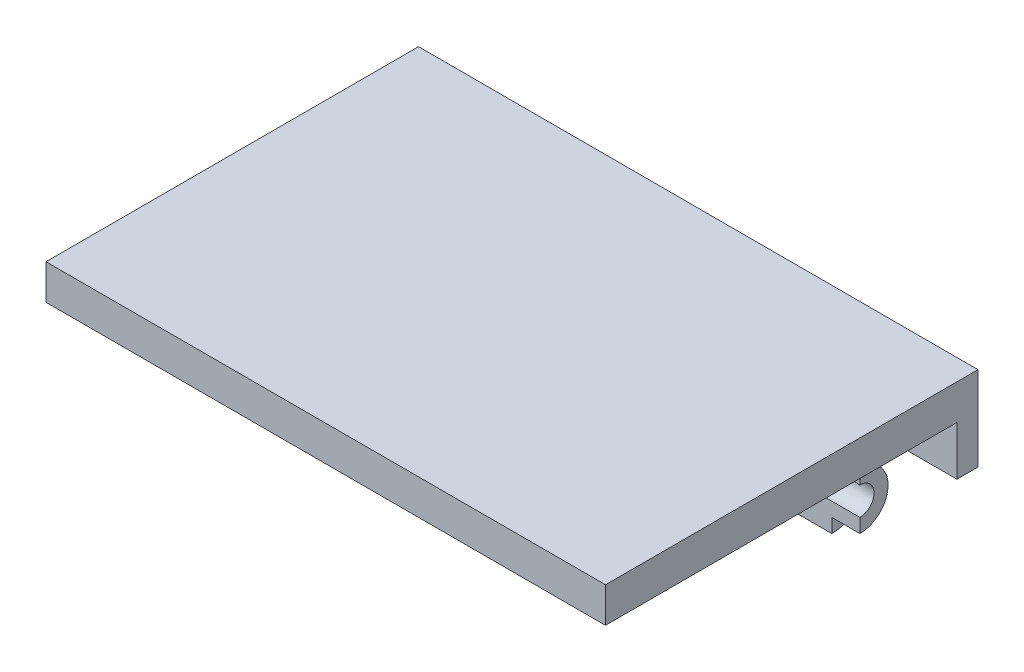
SolidWorks part; units mm, degrees
ref_plane "Ön Düzlem" through (0, 0, 0) normal (0, 0, 1) x (1, 0, 0)
ref_plane "Üst Düzlem" through (0, 0, 0) normal (0, 1, 0) x (1, 0, 0)
ref_plane "Sağ Düzlem" through (0, 0, 0) normal (1, 0, 0) x (0, 0, -1)
sketch "Çizim2" plane through (0, 0, 0) normal (0, 0, 1) x (1, 0, 0)
  line L1 (-47.2438, 23.3082) -> (-7.2438, 23.3082)
  line L2 (-47.2438, 23.3082) -> (-47.2438, 7.3082)
  line L3 (-47.2438, 7.3082) -> (-7.2438, 7.3082)
  line L4 (-7.2438, 23.3082) -> (-7.2438, 7.3082)
extrude "Yükseklik-Ekstrüzyon4" add sketch "Çizim2" along normal blind 9
sketch "Çizim3" plane through (-7.2438, 0, 0) normal (1, 0, 0) x (0, 0, -1)
  line L0 (-9, 7.3082) -> (-9, 23.3082) construction
  line L1 (-9, 21.3082) -> (-9, 9.3082)
  arc A0 (-9, 11.3082) -> (-9, 19.3082) centre (-9, 15.3082) ccw
  arc A1 (-9, 9.3082) -> (-9, 21.3082) centre (-9, 15.3082) ccw
  line M1 (0, 7.3082) -> (0, 23.3082)
  line M2 (0, 23.3082) -> (-9, 23.3082)
  line M3 (-9, 23.3082) -> (-9, 7.3082)
  line M4 (-9, 7.3082) -> (0, 7.3082)
extrude "Yükseklik-Ekstrüzyon5" add sketch "Çizim3" along normal blind 2 and the other way blind 42 contours A1 L1 A0 M3 region at (-7.2438, 15.3082, 3.1342)
extrude "Yükseklik-Ekstrüzyon6" add sketch "Çizim3<3>" along normal blind 6 and the other way blind 46 contours L1 A0 region at (-7.2438, 15.3082, 7.3023)
sketch "Çizim3<3>" plane through (-7.2438, 0, 0) normal (1, 0, 0) x (0, 0, -1) same geometry as "Çizim3"
sketch "Çizim4" plane through (-1.2438, 0, 0) normal (1, 0, 0) x (0, 0, -1)
  line L0 (-9, 17.3082) -> (-9, 13.3082)
  arc A3 (-9, 13.3082) -> (-9, 17.3082) centre (-9, 15.3082) ccw
extrude "Kes-Ekstrüzyon1" cut sketch "Çizim4" against normal blind 52
extrude "Kes-Ekstrüzyon2" cut sketch "Çizim3<4>" against normal blind 52 and the other way through all contours A1 L1 M4 M1 M2 M3 region at (-7.2438, 22.3082, 8.8164)
sketch "Çizim3<4>" plane through (-7.2438, 0, 0) normal (1, 0, 0) x (0, 0, -1) same geometry as "Çizim3"
sketch "Çizim7" plane through (-5.2438, 0, 0) normal (1, 0, 0) x (0, 0, -1)
  line L0 (-5, 19.7803) -> (-5, 24.3082)
  line L3 (-9, 21.3082) -> (-9, 24.3082)
  line L4 (-9, 24.3082) -> (-5, 24.3082)
  arc A1 (-9, 21.3082) -> (-5, 19.7803) centre (-9, 15.3082) cw
extrude "Yükseklik-Ekstrüzyon7" add sketch "Çizim7" against normal blind 44
sketch "Çizim8" plane through (0, 0, 9) normal (0, 0, 1) x (1, 0, 0)
  line L0 (-7.4438, 24.3082) -> (-7.4438, 21.3082)
  line L1 (-49.2438, 24.3082) -> (-47.0438, 24.3082)
  line L2 (-49.2438, 24.3082) -> (-49.2438, 22.3082)
  line L5 (-5.2438, 24.3082) -> (-7.4438, 24.3082)
  line L6 (-5.2438, 24.3082) -> (-5.2438, 22.3082)
  line L9 (-7.4438, 21.3082) -> (-5.2438, 21.3082)
  line L10 (-5.2438, 24.3082) -> (-5.2438, 19.3082) construction
  line L11 (-5.2438, 21.3082) -> (-5.2438, 22.3082)
  line L12 (-47.0438, 24.3082) -> (-47.0438, 21.3082)
  line L13 (-47.0438, 21.3082) -> (-49.2438, 21.3082)
  line L14 (-49.2438, 24.3082) -> (-49.2438, 19.3082) construction
  line L15 (-49.2438, 21.3082) -> (-49.2438, 22.3082)
extrude "Kes-Ekstrüzyon4" cut sketch "Çizim8" against normal blind 44 contours L6 L11 L9 L0 L5 | L2 L15 L13 L12 L1
sketch "Çizim10" plane through (-5.2438, 0, 0) normal (1, 0, 0) x (0, 0, -1)
  line L1 (-9, 21.3082) -> (-5, 21.3082)
  line L2 (-5, 21.3082) -> (-5, 19.7803)
  arc A0 (-9, 21.3082) -> (-5, 19.7803) centre (-9, 15.3082) cw
extrude "Kes-Ekstrüzyon8" cut sketch "Çizim7<3>" against normal blind 2.2 contours A1 L0 L4 L3
sketch "Çizim7<3>" plane through (-5.2438, 0, 0) normal (1, 0, 0) x (0, 0, -1) same geometry as "Çizim7"
sketch "Çizim12" plane through (-49.2438, 0, 0) normal (-1, 0, 0) x (0, 0, 1)
  line L0 (5, 19.7803) -> (5, 21.3082)
  line L1 (5, 21.3082) -> (9, 21.3082)
  arc A0 (5, 19.7803) -> (9, 21.3082) centre (9, 15.3082) cw
extrude "Kes-Ekstrüzyon9" cut sketch "Çizim12" against normal blind 2.2
sketch "Çizim14" plane through (0, 24.3082, 0) normal (0, 1, 0) x (1, 0, 0)
  line L0 (-47.0438, -5) -> (-47.0438, -9) construction
  line L1 (-7.4438, -9) -> (-47.0438, -9)
  line L2 (-7.4438, -9) -> (-7.4438, -6)
  line L3 (-7.4438, -6) -> (-47.0438, -6)
  line L4 (-47.0438, -9) -> (-47.0438, -6)
extrude "aralik_eks" add sketch "Çizim14" along normal blind 0.6
sketch "Çizim15" plane through (0, 24.9082, 0) normal (0, 1, 0) x (1, 0, 0)
  line L0 (-53.2438, -9) -> (-49.2438, -9) construction
  line L1 (-47.0438, -6) -> (-67.0438, -6)
  line L3 (-47.0438, -9) -> (-67.0438, -9)
  line L4 (-67.0438, -6) -> (-67.0438, -9)
  line L5 (-7.4438, -9) -> (-5.2438, -9) construction
  line L6 (-7.4438, -6) -> (12.5562, -6)
  line L8 (-7.4438, -9) -> (12.5562, -9)
  line L9 (12.5562, -6) -> (12.5562, -9)
  line L10 (-47.0438, -9) -> (-7.4438, -9)
  line L11 (-7.4438, -6) -> (-47.0438, -6)
extrude "Yükseklik-Ekstrüzyon9" add sketch "Çizim15" along normal blind 12
sketch "Çizim16" plane through (0, 0, 9) normal (0, 0, 1) x (1, 0, 0)
  line L1 (-67.0438, 36.9082) -> (12.5562, 36.9082)
  line L3 (-64.0438, 35.3082) -> (9.5562, 35.3082)
  line L12 (12.5562, 36.9082) -> (12.5562, 31.9082)
  line L13 (12.5562, 36.9082) -> (12.5562, 24.9082) construction
  line L14 (12.5562, 31.9082) -> (9.5562, 31.9082)
  line L15 (9.5562, 31.9082) -> (9.5562, 35.3082)
  line L18 (-64.0438, 31.9082) -> (-64.0438, 35.3082)
  line L19 (-67.0438, 31.9082) -> (-67.0438, 36.9082)
  line L20 (-64.0438, 31.9082) -> (-67.0438, 31.9082)
extrude "Yükseklik-Ekstrüzyon10" add sketch "Çizim16" along normal blind 50
sketch "Çizim17" plane through (0, 35.3082, 0) normal (0, -1, 0) x (1, 0, 0)
  line L0 (9.5562, 59) -> (9.5562, 9) construction
  line L1 (-64.0438, 59) -> (9.5562, 59)
  line L2 (-64.0438, 59) -> (-64.0438, 56)
  line L3 (-64.0438, 56) -> (-59.1438, 56)
  line L4 (9.5562, 59) -> (9.5562, 56)
  line L13 (-64.0438, 51.1) -> (-59.1438, 51.1)
  line L14 (-59.1438, 56) -> (-64.0438, 56)
  line L15 (-64.0438, 56) -> (-64.0438, 51.1)
  line L16 (-59.1438, 51.1) -> (-59.1438, 56)
  line L17 (4.6562, 56) -> (4.6562, 51.1)
  line L18 (9.5562, 56) -> (4.6562, 56)
  line L19 (4.6562, 51.1) -> (9.5562, 51.1)
  line L20 (9.5562, 51.1) -> (9.5562, 56)
  line L21 (4.6562, 56) -> (9.5562, 56)
  line L22 (-64.0438, 56) -> (9.5562, 56)
  line L25 (9.5562, 12) -> (4.6562, 12)
  line L26 (9.5562, 16.9) -> (9.5562, 12)
  line L27 (4.6562, 16.9) -> (9.5562, 16.9)
  line L28 (4.6562, 12) -> (4.6562, 16.9)
  line L29 (-64.0438, 12) -> (-59.1438, 12)
  line L30 (-64.0438, 12) -> (-64.0438, 16.9)
  line L31 (-59.1438, 16.9) -> (-59.1438, 12)
  line L32 (-64.0438, 16.9) -> (-59.1438, 16.9)
  circle A4 centre (-61.5938, 53.55) radius 1
  circle A5 centre (-61.5938, 53.55) radius 1.95
  circle A6 centre (7.1062, 53.55) radius 1
  circle A7 centre (7.1062, 53.55) radius 1.95
  circle A8 centre (7.1062, 14.45) radius 1.95
  circle A9 centre (7.1062, 14.45) radius 1
  circle A10 centre (-61.5938, 14.45) radius 1.95
  circle A11 centre (-61.5938, 14.45) radius 1
extrude "Yükseklik-Ekstrüzyon11" add sketch "Çizim17" along normal blind 3.4 contours L3 L22 L18 L29 | L13 L16 L3 A5 | L17 L19 L18 A7 | L28 L25 L27 A8 | L32 L29 L31 A10 region at (-27.2438, 35.3082, 57.5) region at (-61.5938, 35.3082, 55.9307) region at (9.4869, 35.3082, 53.55) region at (7.1062, 35.3082, 12.0693) region at (-63.9745, 35.3082, 14.45)
sketch "Çizim18" plane through (0, 0, 9) normal (0, 0, 1) x (1, 0, 0)
  line L0 (-39.5438, 28.3082) -> (-39.5438, 17.3082)
  line L1 (-53.2438, 17.3082) -> (-1.2438, 17.3082) construction
  line L2 (-64.0438, 35.3082) -> (9.5562, 35.3082) construction
  line L3 (-47.0438, 35.3082) -> (-7.4438, 35.3082)
  line L7 (-39.5438, 28.3082) -> (-47.0438, 35.3082)
  line L8 (-14.9438, 28.3082) -> (-7.4438, 35.3082)
  line L9 (-14.9438, 28.3082) -> (-14.9438, 17.3082)
  line L12 (-36.3066, 14.7608) -> (-18.181, 14.7608)
  arc A0 (-39.5438, 17.3082) -> (-36.3066, 14.7608) centre (-27.2438, 29.6082) ccw
  arc A1 (-18.181, 14.7608) -> (-14.9438, 17.3082) centre (-27.2438, 29.6082) ccw
extrude "Kes-Ekstrüzyon11" cut sketch "Çizim18" against normal blind 0.8
sketch "Çizim19" plane through (0, 0, 9) normal (0, 0, 1) x (1, 0, 0)
  line L3 (-10.2438, 18.6069) -> (-8.6257, 19.7825)
  line L4 (-8.6257, 19.7825) -> (-9.2438, 21.6846)
  line L5 (-9.2438, 21.6846) -> (-11.2438, 21.6846)
  line L6 (-11.2438, 21.6846) -> (-11.8618, 19.7825)
  line L7 (-11.8618, 19.7825) -> (-10.2438, 18.6069)
  line L8 (-42.6257, 19.7825) -> (-44.2438, 18.6069)
  line L9 (-43.2438, 21.6846) -> (-42.6257, 19.7825)
  line L10 (-45.2438, 21.6846) -> (-43.2438, 21.6846)
  line L11 (-45.8618, 19.7825) -> (-45.2438, 21.6846)
  line L12 (-44.2438, 18.6069) -> (-45.8618, 19.7825)
extrude "Kes-Ekstrüzyon12" cut sketch "Çizim19" against normal blind 2
